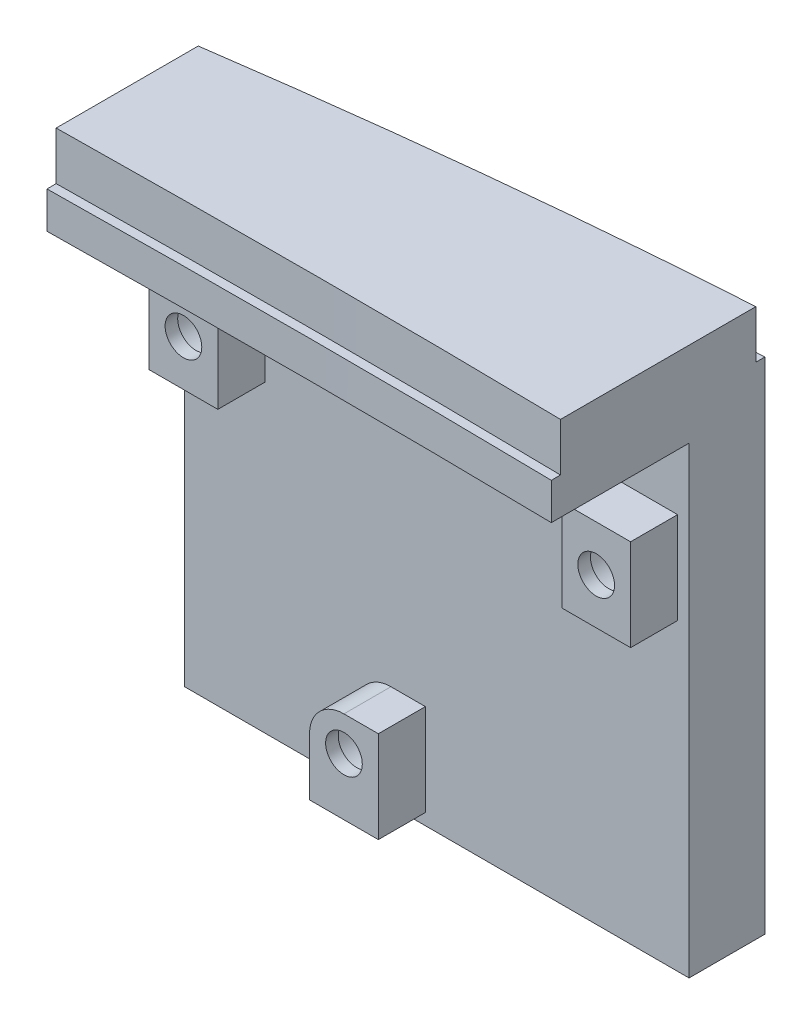
SolidWorks part; units mm, degrees
ref_plane "Front Plane" through (0, 0, 0) normal (0, 0, 1) x (1, 0, 0)
ref_plane "Top Plane" through (0, 0, 0) normal (0, 1, 0) x (1, 0, 0)
ref_plane "Right Plane" through (0, 0, 0) normal (1, 0, 0) x (0, 0, -1)
sketch "Sketch1" plane through (0, 0, 0) normal (0, 1, 0) x (1, 0, 0)
  line L0 (-144.1303, -12.9929) -> (155.8697, -12.8308) construction
  line L1 (-29.3738, 9.8314) -> (-29.3738, -4.1686)
  line L2 (14.6262, 14.4548) -> (14.6262, -4.183)
  line L5 (-29.3738, -2.9686) -> (14.6262, -2.9686)
  line L12 (-51.1303, 9.4041) -> (-59.1513, -7.7971) construction
  line L13 (-109.8536, -6.9996) -> (-109.986, -6.1605)
  circle A2 centre (-36.6303, 2.3202) radius 4.25
  arc A9 (-58.7697, -6.9788) -> (-58.7632, -6.9861) centre (-51.1303, -0.0856) ccw
  ellipse E0 centre (-36.6303, 2.3202) end of major axis (-36.1292, -4.0323) minor radius 5.05
  spline S0 degree 13 poles (-110.7235, -3.2524) (-98.8326, -0.2567) (-86.3944, 2.6358) (-73.4943, 5.427) (-60.2589, 8.0815) (-46.8275, 10.5453) (-33.3355, 12.7584) (-19.9065, 14.665) (-6.6486, 16.2187) (6.3449, 17.3865) (18.9944, 18.15) (31.2324, 18.5052) (43.0009, 18.4619) (54.25, 18.0415) knots 0.038912 0.038912 0.038912 0.038912 0.038912 0.038912 0.038912 0.038912 0.038912 0.038912 0.038912 0.038912 0.038912 0.038912 0.206425 0.206425 0.206425 0.206425 0.206425 0.206425 0.206425 0.206425 0.206425 0.206425 0.206425 0.206425 0.206425 0.206425
  spline S1 degree 3 poles (-105.7874, -5.9402) (-105.4515, -5.8576) (-103.7907, -5.4506) (-99.0842, -4.3142) (-91.5415, -2.5615) (-82.0457, -0.4684) (-69.1527, 2.2208) (-52.7063, 5.3568) (-32.7854, 8.6244) (-12.9944, 11.2716) (3.1558, 12.8711) (15.7533, 13.7541) (25.0163, 14.2135) (32.556, 14.4255) (38.4824, 14.4928) (41.3869, 14.4927) (42.8464, 14.4842) knots 0.043242 0.043242 0.043242 0.043242 0.044325 0.048583 0.058255 0.067926 0.077598 0.096941 0.116284 0.135628 0.154971 0.164642 0.174314 0.183986 0.188821 0.193657 0.193657 0.193657 0.193657
  spline S2 degree 3 poles (42.3412, -4.3021) (39.1703, -4.1474) (32.8439, -3.8739) (20.0493, -3.4589) (3.9637, -3.1861) (-15.3945, -3.1849) (-34.7131, -3.4228) (-53.9413, -3.8315) (-69.8279, -4.2978) (-82.3956, -4.7634) (-91.7251, -5.1693) (-99.1578, -5.5509) (-103.8174, -5.8207) (-105.4427, -5.9191) (-105.7874, -5.9402) knots 0.702444 0.702444 0.702444 0.702444 0.71714 0.731836 0.761227 0.790619 0.820011 0.849403 0.878795 0.89349 0.908186 0.922882 0.929138 0.930826 0.930826 0.930826 0.930826
  spline S3 degree 3 poles (-109.986, -6.1605) (-109.4642, -6.0291) (-108.4175, -5.7667) (-103.5943, -4.5692) (-94.8971, -2.4925) (-82.0108, 0.3758) (-63.7471, 4.1371) (-40.3543, 8.3552) (-16.9896, 11.6162) (1.2883, 13.4985) (14.7075, 14.5233) (27.7627, 15.1448) (36.8021, 15.2972) (42.0404, 15.2892) (43.1567, 15.2825) (43.6671, 15.2784) knots 0.038912 0.038912 0.038912 0.038912 0.040616 0.04232 0.054528 0.06816 0.081792 0.109056 0.13632 0.149952 0.163584 0.177216 0.190848 0.192861 0.194565 0.194565 0.194565 0.194565
  spline S4 degree 13 poles (52.5193, -8.6666) (40.2713, -7.9192) (27.7839, -7.3485) (15.1503, -6.9773) (2.4425, -6.804) (-10.2886, -6.8041) (-23.0116, -6.9375) (-35.7087, -7.1592) (-48.3688, -7.4339) (-60.9767, -7.7494) (-73.5011, -8.1244) (-85.8777, -8.6024) (-97.9897, -9.2254) (-109.6522, -9.993) knots 0.686195 0.686195 0.686195 0.686195 0.686195 0.686195 0.686195 0.686195 0.686195 0.686195 0.686195 0.686195 0.686195 0.686195 0.937578 0.937578 0.937578 0.937578 0.937578 0.937578 0.937578 0.937578 0.937578 0.937578 0.937578 0.937578 0.937578 0.937578
  spline S5 degree 3 poles (-110.5235, -4.0272) (-108.9029, -3.6189) (-105.6763, -2.8183) (-99.0735, -1.2268) (-90.6514, 0.7176) (-80.2925, 2.9758) (-67.9991, 5.4979) (-58.7506, 7.2436) (-50.652, 8.6798) (-47.6807, 9.1904) (-44.5606, 9.7093) (-38.2765, 10.745) (-25.0157, 12.7601) (-5.2278, 15.1631) (12.1229, 16.5847) (25.5727, 17.2429) (35.4177, 17.4948) (43.3901, 17.504) (49.633, 17.3925) (52.6803, 17.2987) (54.2127, 17.2415) knots 0.038912 0.038912 0.038912 0.038912 0.044146 0.049381 0.059851 0.07032 0.08079 0.096446 0.097403 0.1044 0.105092 0.106475 0.122668 0.143607 0.164546 0.175016 0.185486 0.195955 0.20119 0.206425 0.206425 0.206425 0.206425
  spline S6 degree 3 poles (52.5681, -7.868) (50.9024, -7.7664) (47.578, -7.5733) (40.8667, -7.2231) (32.4163, -6.8574) (22.195, -6.5335) (8.4979, -6.2488) (-8.6998, -6.1472) (-26.1679, -6.3047) (-37.8303, -6.5029) (-44.675, -6.6412) (-49.0049, -6.7375) (-53.5282, -6.8475) (-56.9797, -6.937) (-62.6027, -7.0912) (-70.3002, -7.3251) (-80.3346, -7.6831) (-90.3076, -8.1048) (-98.4897, -8.5174) (-104.9445, -8.8903) (-108.1134, -9.09) (-109.7048, -9.1947) knots 0.686195 0.686195 0.686195 0.686195 0.69405 0.701906 0.717617 0.733329 0.74904 0.780463 0.811886 0.82883 0.833892 0.843309 0.848739 0.854731 0.859237 0.874732 0.890444 0.906155 0.921867 0.929722 0.937578 0.937578 0.937578 0.937578
  spline S7 degree 3 poles (43.1189, -5.1414) (42.5664, -5.1139) (40.3515, -5.0059) (33.6908, -4.7068) (23.0612, -4.3421) (5.0464, -3.9837) (-17.5716, -3.9643) (-44.6283, -4.3923) (-66.9803, -4.9899) (-84.5965, -5.6437) (-96.3916, -6.1935) (-104.7586, -6.6717) (-108.8142, -6.9312) (-109.8536, -6.9996) knots 0.701175 0.701175 0.701175 0.701175 0.703751 0.711493 0.7321 0.752708 0.793923 0.835139 0.876354 0.896962 0.917569 0.932426 0.937578 0.937578 0.937578 0.937578
  spline S8 degree 3 poles (43.0791, -5.9404) (39.8994, -5.7822) (33.5559, -5.5021) (20.7207, -5.0752) (4.577, -4.7906) (-14.8622, -4.781) (-29.9542, -4.963) (-38.7515, -5.1226) (-41.4966, -5.1769) (-43.935, -5.226) (-46.8305, -5.2883) (-49.9812, -5.3611) (-51.9548, -5.4083) (-59.5635, -5.5969) (-69.6735, -5.894) (-82.18, -6.356) (-91.5501, -6.7627) (-99.2415, -7.157) (-105.3139, -7.5106) (-108.2984, -7.6991) (-109.7967, -7.7977) knots 0.701175 0.701175 0.701175 0.701175 0.71595 0.730726 0.760276 0.789826 0.819377 0.829214 0.830132 0.831967 0.840401 0.843428 0.846456 0.849484 0.878477 0.893252 0.908028 0.922803 0.93019 0.937578 0.937578 0.937578 0.937578
  spline S9 degree 3 poles (-110.1814, -5.3848) (-108.6794, -5.0063) (-105.6878, -4.2632) (-99.5742, -2.785) (-91.7846, -0.9758) (-82.2124, 1.1324) (-69.613, 3.7573) (-59.5108, 5.6872) (-50.135, 7.3499) (-46.7114, 7.9355) (-40.1955, 9.0106) (-29.5503, 10.6773) (-12.6029, 12.9298) (3.6765, 14.5228) (16.3735, 15.3941) (25.7087, 15.8415) (33.3064, 16.0409) (39.2778, 16.0967) (42.204, 16.0903) (43.6745, 16.0785) knots 0.038912 0.038912 0.038912 0.038912 0.043776 0.04864 0.058368 0.068097 0.077825 0.096092 0.09776 0.105207 0.106069 0.116738 0.136195 0.155652 0.16538 0.175108 0.184837 0.189701 0.194565 0.194565 0.194565 0.194565
  dimension "D1" = 8.5
  dimension "D2" = 14
  dimension "D3" = 44
  dimension "D4" = 1.2
extrude "Boss-Extrude2" add sketch "Sketch1" against normal blind 47.8 contours S3 L1 S1 L2 | S1 L1 L5 L2 | S2 L2 L5 L1 | S7 L2 S2 L1 region at (-7.4038, 0, -12.035) region at (-6.2065, 0, -4.396) region at (-7.397, 0, 3.1176) region at (-7.3732, 0, 3.6567)
extrude "Cut-Extrude1" cut sketch "Sketch1<3>" against normal blind 4.2 contours S7 L2 S2 L1 | S3 L1 S1 L2 region at (-7.4038, 0, -12.035) region at (-7.3732, 0, 3.6567)
sketch "Sketch1<3>" plane through (0, 0, 0) normal (0, 1, 0) x (1, 0, 0) same geometry as "Sketch1"
sketch "Sketch2" plane through (0, 0, 0) normal (0, 1, 0) x (1, 0, 0)
  line L0 (-29.3738, 7.8314) -> (14.6262, 7.8314)
  line L1 (-29.3738, 9.8314) -> (-29.3738, -4.1686) construction
  line L2 (14.6262, 14.4548) -> (14.6262, -4.183) construction
  line L3 (-29.3738, -2.9686) -> (14.6262, -2.9686) construction
  line L4 (-29.3738, -2.9686) -> (14.6262, -2.9686)
  line L5 (14.6262, 14.4548) -> (14.6262, -4.183)
  line L6 (-29.3738, 9.8314) -> (-29.3738, -4.1686)
  spline S0 degree 3 poles (-947.9599, -138.3998) (370.8641, -85.6061) (232.6754, -13.6415) (33.6908, -4.7068) (23.0612, -4.3421) (5.0464, -3.9837) (-17.5716, -3.9643) (-44.6283, -4.3923) (-66.9803, -4.9899) (-84.5965, -5.6437) (-96.3916, -6.1935) (-248.8544, -14.9069) (-311.486, -54.3396) (882.4768, -130.5168) knots -0.19176 -0.19176 -0.19176 -0.19176 0.703751 0.711493 0.7321 0.752708 0.793923 0.835139 0.876354 0.896962 0.917569 0.932426 1.637069 1.637069 1.637069 1.637069 only from (43.1189, -5.1414) to (-109.8536, -6.9996) construction
  spline S1 degree 3 poles (43.1189, -5.1414) (42.5664, -5.1139) (40.3515, -5.0059) (33.6908, -4.7068) (23.0612, -4.3421) (5.0464, -3.9837) (-17.5716, -3.9643) (-44.6283, -4.3923) (-66.9803, -4.9899) (-84.5965, -5.6437) (-96.3916, -6.1935) (-104.7586, -6.6717) (-108.8142, -6.9312) (-109.8536, -6.9996) knots 0.701175 0.701175 0.701175 0.701175 0.703751 0.711493 0.7321 0.752708 0.793923 0.835139 0.876354 0.896962 0.917569 0.932426 0.937578 0.937578 0.937578 0.937578
  spline M3 degree 3 poles (-105.7874, -5.9402) (-105.4427, -5.9191) (-103.8174, -5.8207) (-99.1578, -5.5509) (-91.7251, -5.1693) (-82.3956, -4.7634) (-69.8279, -4.2978) (-53.9413, -3.8315) (-34.7131, -3.4228) (-15.3945, -3.1849) (3.9637, -3.1861) (20.0493, -3.4589) (32.8439, -3.8739) (39.1703, -4.1474) (42.3412, -4.3021) knots 0.702444 0.702444 0.702444 0.702444 0.704132 0.710388 0.725084 0.739779 0.754475 0.783867 0.813259 0.842651 0.872042 0.901434 0.91613 0.930826 0.930826 0.930826 0.930826 only from (-29.3738, -3.3687) to (14.6262, -3.383)
  line M4 (14.6262, -3.383) -> (14.6262, 13.6533)
  line M6 (-29.3738, 9.0233) -> (-29.3738, -3.3687)
  dimension "D1" = 2
extrude "Cut-Extrude2" cut sketch "Sketch2" against normal through all from offset 7.4 contours L4 L0 M6 M4 | L4 M6 M3 M4 | S1 L5 L6 M3 region at (-7.3738, 0, -2.4314) region at (-7.3795, 0, 3.5139) offset against normal yes
sketch "Sketch3" plane through (0, 0, -7.8314) normal (0, 0, 1) x (1, 0, 0)
  line L0 (14.6262, -47.8) -> (14.6262, -7.4) construction
  line L1 (-29.3738, -47.8) -> (14.6262, -47.8) construction
  circle A0 centre (-11.3738, -41.8) radius 2.5
  circle A1 centre (-25.3738, -17.3) radius 2.5
  circle A2 centre (10.6262, -17.3) radius 2.5
  dimension "D1" = 5
  dimension "D2" = 14
  dimension "D3" = 36
  dimension "D4" = 4
  dimension "D5" = 24.5
  dimension "D6" = 6
extrude "Cut-Extrude3" cut sketch "Sketch3" against normal through all
sketch "Sketch4" plane through (0, 0, -7.8314) normal (0, 0, 1) x (1, 0, 0)
  line L0 (-28.3738, -13.3) -> (-22.3738, -13.3)
  line L1 (-28.3738, -13.3) -> (-28.3738, -21.3)
  line L2 (-28.3738, -21.3) -> (-22.3738, -21.3)
  line L3 (-22.3738, -13.3) -> (-22.3738, -21.3)
  line L4 (7.6262, -13.3) -> (13.6262, -13.3)
  line L5 (7.6262, -13.3) -> (7.6262, -21.3)
  line L6 (7.6262, -21.3) -> (13.6262, -21.3)
  line L7 (13.6262, -13.3) -> (13.6262, -21.3)
  line L9 (-14.3738, -41.8) -> (-14.3738, -46.8)
  line L10 (-14.3738, -46.8) -> (-8.3738, -46.8)
  line L11 (-8.3738, -38.8) -> (-8.3738, -46.8)
  line L12 (-29.3738, -47.8) -> (-29.3738, -7.4) construction
  line L13 (14.6262, -47.8) -> (14.6262, -7.4) construction
  line L14 (-29.3738, -47.8) -> (14.6262, -47.8) construction
  line L15 (-11.3738, -38.8) -> (-8.3738, -38.8)
  arc A0 (-11.3738, -38.8) -> (-14.3738, -41.8) centre (-11.3738, -41.8) ccw
  point P21 (0, 0)
  point P23 (-25.3738, -21.3)
  dimension "D11" = 28.5
  dimension "D12" = 3
  dimension "D1" = 1
  dimension "D2" = 8
  dimension "D3" = 6
  dimension "D4" = 6
  dimension "D5" = 8
  dimension "D6" = 1
  dimension "D7" = 1
  dimension "D8" = 8
  dimension "D9" = 6
  dimension "D10" = 14
extrude "Boss-Extrude4" add sketch "Sketch4" along normal blind 4.1
sketch "Sketch8" plane through (0, 0, -7.8314) normal (0, 0, 1) x (1, 0, 0)
  circle A0 centre (10.6262, -17.3) radius 1.6
  circle A1 centre (-25.3738, -17.3) radius 1.6
  circle A2 centre (-11.3738, -41.8) radius 1.6
  dimension "D1" = 3.2
extrude "Cut-Extrude6" cut sketch "Sketch8" against normal through all both and the other way through all
ref_plane "Plane1" through (0, 0, -11.0314) normal (0, 0, -1) x (-1, 0, 0)
sketch "Sketch9" plane through (0, 0, -11.0314) normal (0, 0, -1) x (-1, 0, 0)
  circle A0 centre (-10.6262, -17.3) radius 2.5
  circle A1 centre (25.3738, -17.3) radius 2.5
  circle A2 centre (11.3738, -41.8) radius 2.5
  point P9 (0, 0)
  dimension "D1" = 5
ref_plane "Plane2" through (0, 0, -14.4314) normal (0, 0, 1) x (1, 0, 0)
sketch "Sketch10" plane through (0, 0, -14.4314) normal (0, 0, 1) x (1, 0, 0)
  circle A0 centre (10.6262, -17.3) radius 3.75
  circle A1 centre (-11.3738, -41.8) radius 3.75
  circle A2 centre (-25.3738, -17.3) radius 3.75
  dimension "D1" = 7.5
loft "Cut-Loft2" cut section "Sketch9" section "Sketch10" connector at (9.8015, -19.6601, -11.0314) connector at (10.9039, -21.0397, -14.4314)
loft "Cut-Loft3" cut section "Sketch10<8>" section "Sketch9<8>" connector at (-23.4751, -14.0662, -14.4314) connector at (-23.9856, -15.2209, -11.0314)
sketch "Sketch10<8>" plane through (0, 0, -14.4314) normal (0, 0, 1) x (1, 0, 0) same geometry as "Sketch10"
sketch "Sketch9<8>" plane through (0, 0, -11.0314) normal (0, 0, -1) x (-1, 0, 0) same geometry as "Sketch9"
loft "Cut-Loft4" cut section "Sketch10<9>" section "Sketch9<9>" connector at (-8.9853, -38.9091, -14.4314) connector at (-9.844, -39.8227, -11.0314)
sketch "Sketch10<9>" plane through (0, 0, -14.4314) normal (0, 0, 1) x (1, 0, 0) same geometry as "Sketch10"
sketch "Sketch9<9>" plane through (0, 0, -11.0314) normal (0, 0, -1) x (-1, 0, 0) same geometry as "Sketch9"
ref_plane "Plane3" through (0, 0, -4.8314) normal (0, 0, 1) x (1, 0, 0)
sketch "Sketch12" plane through (0, 0, -4.8314) normal (0, 0, 1) x (1, 0, 0)
  circle A1 centre (-25.3738, -17.3) radius 2.5
  circle A2 centre (10.6262, -17.3) radius 2.5
  circle A3 centre (-11.3738, -41.8) radius 2.5
  dimension "D1" = 5
extrude "Cut-Extrude10" cut sketch "Sketch12" against normal through all
